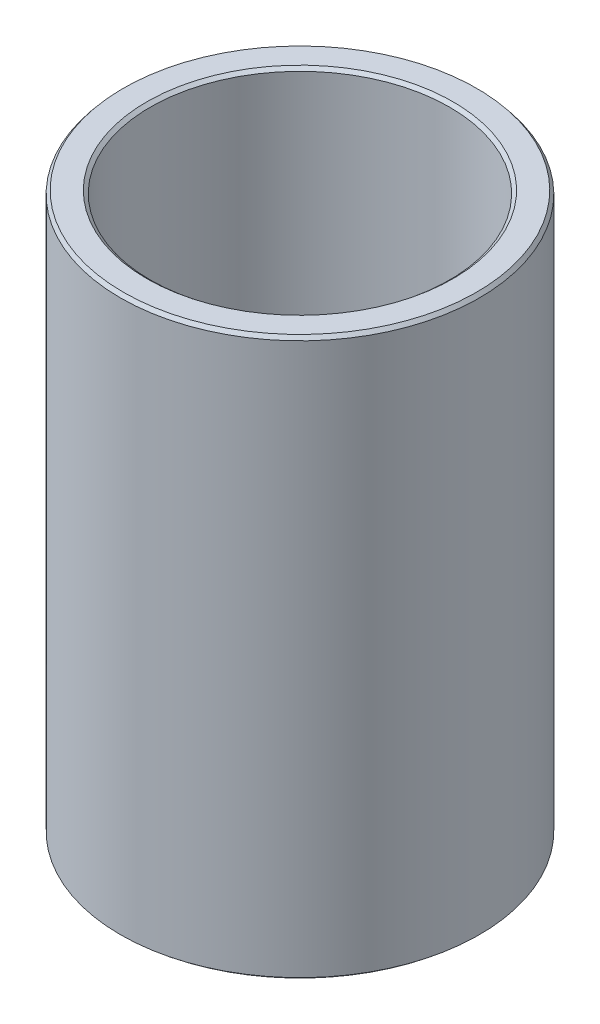
SolidWorks part; units mm, degrees
ref_plane "Front Plane" through (0, 0, 0) normal (0, 0, 1) x (1, 0, 0)
ref_plane "Top Plane" through (0, 0, 0) normal (0, 1, 0) x (1, 0, 0)
ref_plane "Right Plane" through (0, 0, 0) normal (1, 0, 0) x (0, 0, -1)
sketch "Sketch1" plane through (0, 0, 0) normal (0, 1, 0) x (1, 0, 0)
  circle A0 centre (0, 0) radius 40
  dimension "SLEEVE_OD" = 80
extrude "Boss-Extrude1" add sketch "Sketch1" along normal blind 124.3088
sketch "Sketch2" plane through (0, 0, 0) normal (0, 1, 0) x (1, 0, 0)
  circle A0 centre (0, 0) radius 33.3555
  dimension "BORE_D" = 66.7109
extrude "Cut-Extrude1" cut sketch "Sketch2" along normal through all
chamfer "Chamfer1" distance 0.7802 angle 39.278 4 edges at (0, 124.3088, 33.3555) (0, 0, 33.3555) (0, 0, 40) (0, 124.3088, 40) first distance on face at (0, 124.3088, 33.3555) first distance on face at (0, 0, 33.3555) first distance on face at (0, 124.3088, 40)
